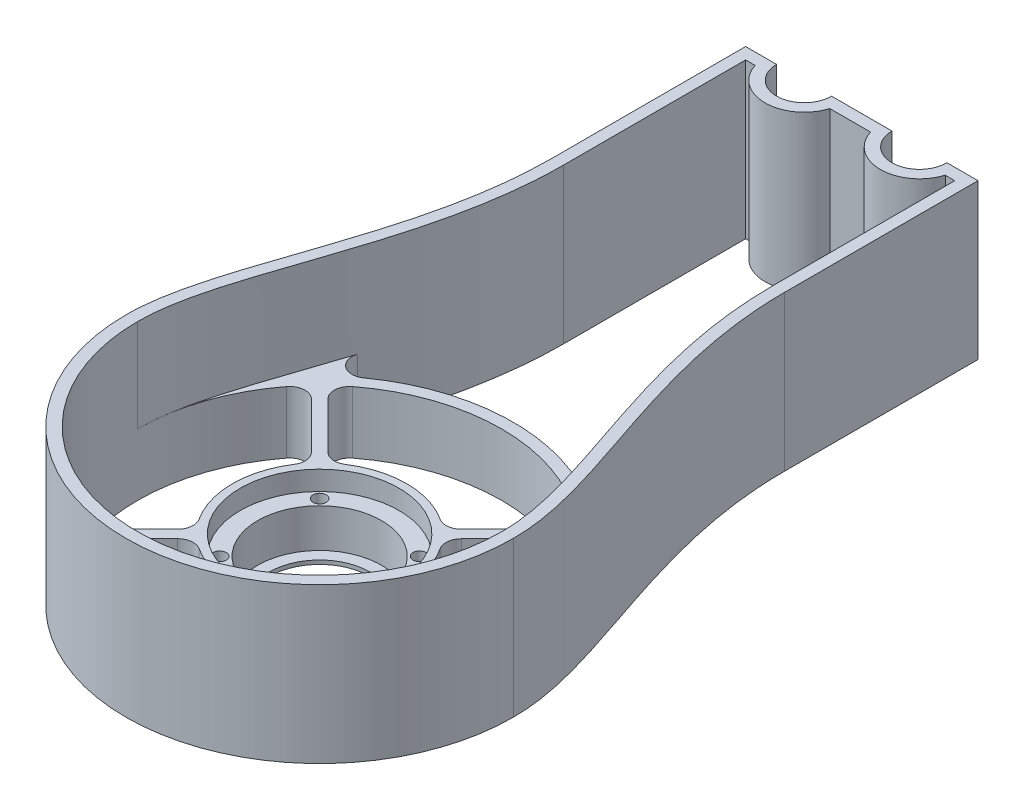
SolidWorks part; units mm, degrees
material "3.1355 (EN-AW 2024)"
ref_plane "Front" through (0, 0, 0) normal (0, 0, 1) x (1, 0, 0)
ref_plane "Top" through (0, 0, 0) normal (0, 1, 0) x (1, 0, 0)
ref_plane "Right" through (0, 0, 0) normal (1, 0, 0) x (0, 0, -1)
sketch "Эскиз1" plane through (0, 0, 0) normal (0, 1, 0) x (1, 0, 0)
  line L0 (0, 0) -> (8, 0)
  line L1 (0, 0) -> (0, -100) construction
  line L2 (0, -12.5175) -> (60, -12.5175) construction
  line L3 (8, 0) -> (22.2, 0) construction
  line L4 (30, -12.5175) -> (30, 0) construction
  line L5 (60, 0) -> (52, 0)
  line L6 (60, 0) -> (60, -100) construction
  line L7 (22.2, 0) -> (37.8, 0)
  line L8 (30, 0) -> (30, -140) construction
  line L9 (0, -80.7644) -> (0, -19.2352) construction
  line L10 (0, 0) -> (0, -50)
  line L11 (60, 0) -> (60, -50)
  arc A0 (22.2, 0) -> (8, 0) centre (15.1, 0) cw
  arc A1 (37.8, 0) -> (52, 0) centre (44.9, 0) ccw
  circle A2 centre (30, -140) radius 47 construction
  circle A3 centre (30, -140) radius 50 construction
  arc A4 (-20, -140) -> (80, -140) centre (30, -140) ccw
  spline S0 degree 3 poles (0, -50) (0, -86.1164) (-20.1607, -116.6426) (-20, -140) knots 0 0 0 0 1 1 1 1
  spline S1 degree 3 poles (60, -50) (60, -86.1164) (80.1607, -116.6426) (80, -140) knots 0 0 0 0 1 1 1 1
  dimension "D3" = 7.1
  dimension "D5" = 94
  dimension "D6" = 100
  dimension "D1" = 60
  dimension "D2" = 8
  dimension "D4" = 140
extrude "Бобышка-Вытянуть1" add sketch "Эскиз1" along normal blind 40
sketch "Эскиз2" plane through (0, 0, 0) normal (0, -1, 0) x (1, 0, 0)
  line L10 (3, 50) -> (3, 3)
  line L11 (3, 3) -> (5.4558, 3)
  line L12 (24.7442, 3) -> (35.2558, 3)
  line L13 (54.5442, 3) -> (57, 3)
  line L14 (57, 3) -> (57, 50)
  line L15 (0, 50) -> (0, 0)
  line L16 (60, 0) -> (60, 50)
  line L17 (52, 0) -> (60, 0)
  line L18 (22.2, 0) -> (37.8, 0)
  line L19 (0, 0) -> (8, 0)
  line L20 (0, 50) -> (0, 0) construction
  line L21 (60, 0) -> (60, 50) construction
  line L22 (52, 0) -> (60, 0) construction
  line L23 (22.2, 0) -> (37.8, 0) construction
  line L24 (0, 0) -> (8, 0) construction
  arc A6 (24.7442, 3) -> (5.4558, 3) centre (15.1, 0) ccw
  arc A7 (54.5442, 3) -> (35.2558, 3) centre (44.9, 0) ccw
  arc A8 (77, 139.9898) -> (-17, 139.9898) centre (30, 140) ccw
  arc A9 (80, 140) -> (-20, 140) centre (30, 140) ccw
  arc A10 (52, 0) -> (37.8, 0) centre (44.9, 0) ccw
  arc A11 (22.2, 0) -> (8, 0) centre (15.1, 0) ccw
  arc A12 (80, 140) -> (-20, 140) centre (30, 140) ccw construction
  arc A13 (52, 0) -> (37.8, 0) centre (44.9, 0) ccw construction
  arc A14 (22.2, 0) -> (8, 0) centre (15.1, 0) ccw construction
  spline S4 degree 1 poles (57, 50) (77, 139.9898) knots 0 0 1 1 construction
  spline S5 degree 1 poles (-17, 139.9898) (3, 50) knots 0 0 1 1 construction
  spline S6 degree 3 poles (2974.8733, 17.0098) (-3143.323, 462.9237) (3099.91, -31.1134) (-2928.364, -504.442) knots -3.750439 -3.750439 -3.750439 -3.750439 4.723475 4.723475 4.723475 4.723475 only from (-20, 140) to (0, 50)
  spline S7 degree 3 poles (2988.4431, -504.4482) (-3039.9457, -31.1192) (3203.3107, 462.9225) (-2914.8159, 17.014) knots -3.723512 -3.723512 -3.723512 -3.723512 4.750412 4.750412 4.750412 4.750412 only from (60, 50) to (80, 140)
  spline S8 degree 3 poles (-20, 140) (-20.1607, 116.6426) (0, 86.1164) (0, 50) knots 0 0 0 0 1 1 1 1 construction
  spline S9 degree 3 poles (60, 50) (60, 86.1164) (80.1607, 116.6426) (80, 140) knots 0 0 0 0 1 1 1 1 construction
  spline S10 degree 3 poles (57, 50) (57, 51.1576) (57.0406, 53.4814) (57.2737, 58.0563) (57.83, 63.6856) (58.8582, 70.2787) (60.6258, 78.8545) (63.4224, 89.1625) (67.2233, 100.8564) (70.9826, 111.8507) (73.6803, 120.399) (75.3443, 126.8384) (76.2901, 131.4596) (76.7833, 135.1228) (76.9778, 137.9476) (77.0047, 139.3043) (77, 139.9898) knots 0 0 0 0 0.031255 0.062509 0.125019 0.187528 0.250037 0.375056 0.500075 0.625093 0.750112 0.812622 0.875131 0.93764 0.968895 1.00015 1.00015 1.00015 1.00015
  spline S11 degree 3 poles (-17, 139.9898) (-17.0047, 139.3043) (-16.9778, 137.9476) (-16.7833, 135.1228) (-16.2901, 131.4596) (-15.3443, 126.8384) (-13.6803, 120.399) (-10.9826, 111.8507) (-7.2233, 100.8564) (-3.4224, 89.1625) (-0.6258, 78.8545) (1.1418, 70.2787) (2.17, 63.6856) (2.7263, 58.0563) (2.9594, 53.4814) (3, 51.1576) (3, 50) knots -0.00015 -0.00015 -0.00015 -0.00015 0.031105 0.06236 0.124869 0.187378 0.249888 0.374907 0.499925 0.624944 0.749963 0.812472 0.874981 0.937491 0.968745 1 1 1 1
  dimension "D1" = 0
  dimension "D2" = 3
extrude "Вырез-Вытянуть1" cut sketch "Эскиз2" against normal through all
sketch "Эскиз3" plane through (0, 0, 0) normal (0, -1, 0) x (1, 0, 0)
  circle A0 centre (30, 140) radius 13
  circle A1 centre (30, 140) radius 22.5
  dimension "D1" = 26
  dimension "D2" = 45
extrude "Бобышка-Вытянуть2" add sketch "Эскиз3" against normal blind 16 separate body
sketch "Эскиз4" plane through (0, 16, 0) normal (0, 1, 0) x (1, 0, 0)
  circle A2 centre (30, -140) radius 20.5
  dimension "D1" = 41
extrude "Вырез-Вытянуть2" cut sketch "Эскиз4" against normal blind 5
sketch "Эскиз5" plane through (0, 11, 0) normal (0, 1, 0) x (1, 0, 0)
  circle A0 centre (30, -140) radius 16
  dimension "D1" = 32
extrude "Вырез-Вытянуть3" cut sketch "Эскиз5" against normal blind 10
sketch "Эскиз6" plane through (0, 11, 0) normal (0, 1, 0) x (1, 0, 0)
  line L0 (30, -140) -> (11.75, -140) construction
  line L1 (30, -140) -> (17.0953, -127.0953) construction
  line L2 (30, -140) -> (42.9047, -127.0953) construction
  line L3 (30, -140) -> (42.9047, -152.9047) construction
  line L4 (30, -140) -> (17.0953, -152.9047) construction
  circle A0 centre (30, -140) radius 18.25 construction
  point P11 (30, -140)
  dimension "D1" = 36.5
  dimension "D2" = 45
  dimension "D3" = 4
hole_wizard "Отверстие с зазором M31" positions "Эскиз8" profile "Эскиз7" hole size "M3" standard "Ansi Metric" end condition through all
sketch "Эскиз8" plane through (0, 11, 0) normal (0, 1, 0) x (1, 0, 0)
  point P0 (17.0953, -127.0953)
  point P3 (42.9047, -127.0953)
  point P6 (42.9047, -152.9047)
  point P9 (17.0953, -152.9047)
sketch "Эскиз7" plane through (17.0953, 11, 127.0953) normal (1, 0, 0) x (0, 0, 1)
  line L0 (0, 0) -> (0, 11)
  line L1 (0, 11) -> (1.7, 11)
  line L2 (1.7, 11) -> (1.7, 0)
  line L5 (1.7, 0) -> (0, 0)
  line L11 (0, -6.35) -> (0, 107.95) construction
  dimension "Диаметр сквозного отверстия" = 3.4
  dimension "Глубина сквозного отверстия" = 11
sketch "Эскиз9" plane through (0, 0, 0) normal (0, -1, 0) x (1, 0, 0)
  arc A0 (-10.5903, 110.8036) -> (70.5903, 110.8036) centre (30, 140) ccw
  arc A2 (-17, 139.9898) -> (77, 139.9898) centre (30, 140) ccw
  spline S1 degree 3 poles (143.2369, 2133.3498) (16.7126, 172.1608) (-19.1444, 169.4132) (-16.7833, 135.1228) (-16.2901, 131.4596) (-15.3443, 126.8384) (-13.6803, 120.399) (-10.9826, 111.8507) (-7.2233, 100.8564) (-3.4224, 89.1625) (-0.6258, 78.8545) (1.1418, 70.2787) (2.17, 63.6856) (2.7263, 58.0563) (6.108, -8.3151) (-50.2325, -100.9504) (-382.6796, 2011.3771) knots -1.392758 -1.392758 -1.392758 -1.392758 0.031105 0.06236 0.124869 0.187378 0.249888 0.374907 0.499925 0.624944 0.749963 0.812472 0.874981 0.937491 0.968745 2.688738 2.688738 2.688738 2.688738 only from (-17, 139.9898) to (3, 50) construction
  spline S2 degree 3 poles (442.6796, 2011.3774) (110.2325, -100.9504) (53.892, -8.3151) (57.2737, 58.0563) (57.83, 63.6856) (58.8582, 70.2787) (60.6258, 78.8545) (63.4224, 89.1625) (67.2233, 100.8564) (70.9826, 111.8507) (73.6803, 120.399) (75.3443, 126.8384) (76.2901, 131.4596) (76.7833, 135.1228) (79.1444, 169.4133) (43.287, 172.1608) (-83.2388, 2133.3791) knots -1.688738 -1.688738 -1.688738 -1.688738 0.031255 0.062509 0.125019 0.187528 0.250037 0.375056 0.500075 0.625093 0.750112 0.812622 0.875131 0.93764 0.968895 2.392765 2.392765 2.392765 2.392765 only from (57, 50) to (77, 139.9898) construction
  spline S3 degree 3 poles (70.5903, 110.8036) (70.6927, 111.1127) (71.9681, 114.9735) (73.6803, 120.399) (75.3443, 126.8384) (76.2901, 131.4596) (76.7833, 135.1228) (76.9778, 137.9476) (77.0047, 139.3043) (77, 139.9898) knots 0.614251 0.614251 0.614251 0.614251 0.625093 0.750112 0.812622 0.875131 0.93764 0.968895 1.00015 1.00015 1.00015 1.00015
  spline S4 degree 3 poles (-17, 139.9898) (-17.0047, 139.3043) (-16.9778, 137.9476) (-16.7833, 135.1228) (-16.2901, 131.4596) (-15.3443, 126.8384) (-13.6803, 120.399) (-11.9681, 114.9735) (-10.6927, 111.1127) (-10.5903, 110.8036) knots -0.00015 -0.00015 -0.00015 -0.00015 0.031105 0.06236 0.124869 0.187378 0.249888 0.374907 0.385749 0.385749 0.385749 0.385749
extrude "Бобышка-Вытянуть3" add sketch "Эскиз9" against normal up to surface (16 mm away) up to face at (30, 16, 160.5)
sketch "Эскиз10" plane through (0, 0, 0) normal (0, -1, 0) x (1, 0, 0)
  line L0 (30, 140) -> (-3.2268, 106.7588) construction
  line L1 (30, 140) -> (-17, 139.9898) construction
  line L2 (13.0616, 154.8102) -> (-4.2847, 172.149)
  line L3 (15.1898, 123.0616) -> (-2.149, 105.7153)
  line L4 (13.068, 125.1825) -> (-4.2708, 107.8362)
  line L5 (31.0609, 138.9396) -> (-2.1659, 105.6984) construction
  line L6 (15.1825, 156.932) -> (-2.1638, 174.2708)
  line L7 (44.8102, 156.9384) -> (62.149, 174.2847)
  line L8 (46.932, 154.8175) -> (64.2708, 172.1638)
  line L9 (46.9384, 125.1898) -> (64.2847, 107.851)
  line L10 (44.8175, 123.068) -> (62.1638, 105.7292)
  circle A0 centre (30, 140) radius 22.5 construction
  arc A1 (13.068, 125.1825) -> (15.1898, 123.0616) centre (30, 140) ccw
  circle A2 centre (30, 140) radius 47 construction
  arc A3 (-4.2708, 107.8362) -> (-2.149, 105.7153) centre (30, 140) ccw
  arc A4 (-2.1638, 174.2708) -> (-4.2847, 172.149) centre (30, 140) ccw
  arc A5 (15.1825, 156.932) -> (13.0616, 154.8102) centre (30, 140) ccw
  arc A6 (64.2708, 172.1638) -> (62.149, 174.2847) centre (30, 140) ccw
  arc A7 (46.932, 154.8175) -> (44.8102, 156.9384) centre (30, 140) ccw
  arc A8 (62.1638, 105.7292) -> (64.2847, 107.851) centre (30, 140) ccw
  arc A9 (44.8175, 123.068) -> (46.9384, 125.1898) centre (30, 140) ccw
  point P5 (28.9391, 141.0604)
  point P9 (-4.2877, 107.8192)
  point P29 (30, 140)
  point P36 (30, 140)
  dimension "D1" = 45
  dimension "D2" = 4
  dimension "D3" = 1.5
extrude "Бобышка-Вытянуть4" add sketch "Эскиз10" against normal up to surface (16 mm away) up to face at (30, 16, 160.5)
fillet "Скругление1" radius 4 2 edges
fillet "Скругление2" radius 4 16 edges at (13.068, 8, 125.1825) (-4.2708, 8, 107.8362) (13.0616, 8, 154.8102) (-4.2847, 8, 172.149) (-2.1638, 8, 174.2708) (15.1825, 8, 156.932) (44.8102, 8, 156.9384) (62.149, 8, 174.2847) (46.932, 8, 154.8175) (64.2708, 8, 172.1638) (46.9384, 8, 125.1898) (64.2847, 8, 107.851) (44.8175, 8, 123.068) (15.1898, 8, 123.0616) (-2.149, 8, 105.7153) (62.1638, 8, 105.7292)
